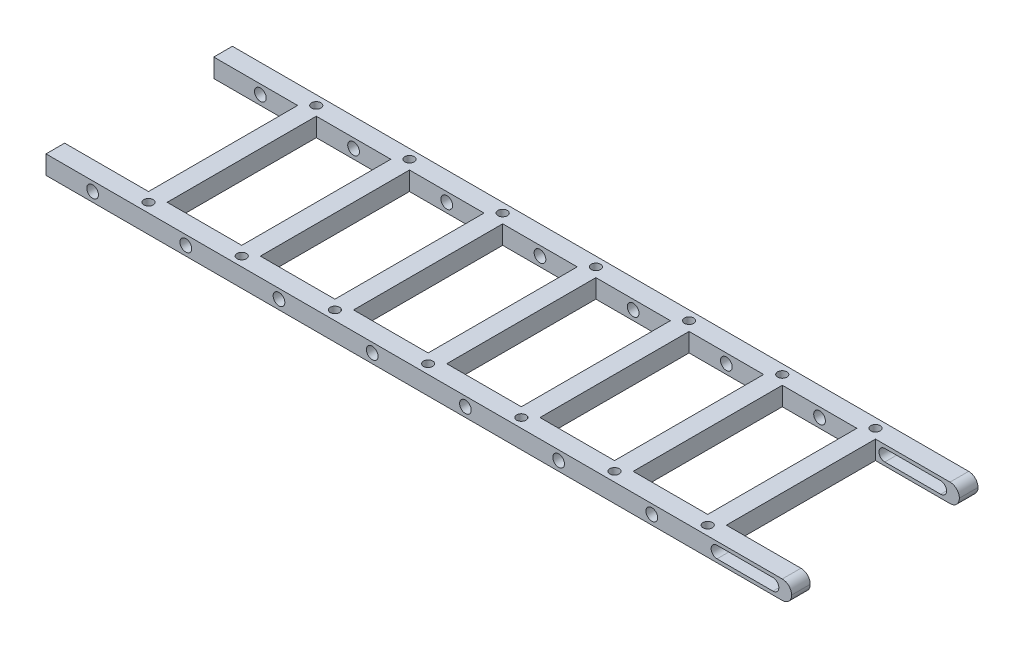
SolidWorks part; units mm, degrees
ref_plane "Front Plane" through (0, 0, 0) normal (0, 0, 1) x (1, 0, 0)
ref_plane "Top Plane" through (0, 0, 0) normal (0, 1, 0) x (1, 0, 0)
ref_plane "Right Plane" through (0, 0, 0) normal (1, 0, 0) x (0, 0, -1)
sketch "Sketch1" plane through (0, 0, 0) normal (0, 1, 0) x (1, 0, 0)
  line L0 (-127, 25.4) -> (-98.425, 25.4)
  line L1 (-127, 31.75) -> (127, 31.75)
  line L2 (-127, 31.75) -> (-127, 25.4)
  line L3 (-127, -31.75) -> (127, -31.75)
  line L4 (127, 31.75) -> (127, 25.4)
  line L8 (-127, -25.4) -> (-98.425, -25.4)
  line L10 (0, 31.75) -> (0, -31.75) construction
  line L11 (-3.175, 25.4) -> (-3.175, -25.4)
  line L12 (98.425, 25.4) -> (98.425, -25.4)
  line L14 (-3.175, 31.75) -> (-3.175, -31.75) construction
  line L15 (-28.575, 25.4) -> (-28.575, -25.4)
  line L16 (-34.925, 25.4) -> (-34.925, -25.4)
  line L17 (-60.325, 25.4) -> (-60.325, -25.4)
  line L18 (-66.675, 25.4) -> (-66.675, -25.4)
  line L19 (-92.075, 25.4) -> (-92.075, -25.4)
  line L22 (-98.425, 25.4) -> (-98.425, -25.4)
  line L23 (-127, -25.4) -> (-127, -31.75)
  line L24 (127, -25.4) -> (127, -31.75)
  line L26 (92.075, 25.4) -> (92.075, -25.4)
  line L27 (66.675, 25.4) -> (66.675, -25.4)
  line L28 (60.325, 25.4) -> (60.325, -25.4)
  line L29 (34.925, 25.4) -> (34.925, -25.4)
  line L30 (28.575, 25.4) -> (28.575, -25.4)
  line L31 (3.175, 25.4) -> (3.175, -25.4)
  line L34 (-92.075, 25.4) -> (-66.675, 25.4)
  line L35 (-92.075, -25.4) -> (-66.675, -25.4)
  line L36 (-28.575, -25.4) -> (-3.175, -25.4)
  line L37 (-60.325, 25.4) -> (-34.925, 25.4)
  line L38 (-28.575, 25.4) -> (-3.175, 25.4)
  line L39 (3.175, 25.4) -> (28.575, 25.4)
  line L40 (3.175, -25.4) -> (28.575, -25.4)
  line L41 (34.925, -25.4) -> (60.325, -25.4)
  line L42 (34.925, 25.4) -> (60.325, 25.4)
  line L43 (66.675, 25.4) -> (92.075, 25.4)
  line L44 (66.675, -25.4) -> (92.075, -25.4)
  line L47 (98.425, -25.4) -> (127, -25.4)
  line L48 (98.425, 25.4) -> (127, 25.4)
  line L49 (-60.325, -25.4) -> (-34.925, -25.4)
  point P0 (0, 0)
  point P16 (0, 0)
  point P18 (0, 0)
  dimension "D1" = 63.5
  dimension "D2" = 127
  dimension "D4" = 3.175
  dimension "D3" = 6.35
  dimension "D14" = 6.35
  dimension "D5" = 6.35
  dimension "D6" = 25.4
  dimension "D7" = 6.35
  dimension "D8" = 25.4
  dimension "D9" = 6.35
  dimension "D10" = 25.4
extrude "Boss-Extrude1" add sketch "Sketch1" against normal blind 6.35
sketch "Sketch2" plane through (0, 0, 31.75) normal (0, 0, 1) x (1, 0, 0)
  line L0 (-111.125, 0) -> (-111.125, -6.35) construction
  line L1 (0, 0) -> (0, -6.35) construction
  line L3 (-127, -6.35) -> (127, -6.35) construction
  line L15 (-66.675, 0) -> (-92.075, 0)
  line L16 (-92.075, 0) -> (-92.075, -6.35)
  line L17 (-92.075, -6.35) -> (-66.675, -6.35)
  line L18 (-66.675, -6.35) -> (-66.675, 0)
  line L19 (-66.675, 0) -> (-92.075, 0) construction
  line L20 (-92.075, 0) -> (-92.075, -6.35) construction
  line L21 (-92.075, -6.35) -> (-66.675, -6.35) construction
  line L22 (-66.675, -6.35) -> (-66.675, 0) construction
  circle A7 centre (-79.375, -3.175) radius 1.9939
  circle A8 centre (-47.625, -3.175) radius 1.9939
  circle A9 centre (-15.875, -3.175) radius 1.9939
  circle A15 centre (-111.125, -3.175) radius 1.9939
  circle A16 centre (15.875, -3.175) radius 1.9939
  circle A17 centre (47.625, -3.175) radius 1.9939
  circle A18 centre (79.375, -3.175) radius 1.9939
  circle A19 centre (111.125, -3.175) radius 1.9939
  point P3 (-79.375, 0)
  point P8 (-92.075, -3.175)
  dimension "D4" = 0
  dimension "D13" = 3.9878
  dimension "D14" = 3.9878
  dimension "D15" = 3.9878
  dimension "D2" = 3.9878
  dimension "D9" = 31.75
  dimension "D10" = 31.75
  dimension "D3" = 31.75
extrude "Cut-Extrude1" cut sketch "Sketch2" against normal up to surface (63.5 mm away) contours A15 | A7 | A8 | A17 | A9 | A16 | A19 | A18 region at (-79.375, -3.175, 31.75) region at (-47.625, -3.175, 31.75) region at (-111.125, -3.175, 31.75) region at (47.625, -3.175, 31.75) up to face at (0, -3.175, -31.75)
sketch "Sketch3" plane through (0, 0, 31.75) normal (0, 0, 1) x (1, 0, 0)
  line L0 (101.6, -3.175) -> (120.65, -3.175) construction
  line L1 (101.6, -1.175) -> (120.65, -1.175)
  line L2 (101.6, -5.175) -> (120.65, -5.175)
  arc A0 (101.6, -1.175) -> (101.6, -5.175) centre (101.6, -3.175) ccw
  arc A1 (120.65, -5.175) -> (120.65, -1.175) centre (120.65, -3.175) ccw
  circle A2 centre (111.125, -3.175) radius 1.9939 construction
  circle A3 centre (111.125, -3.175) radius 1.9939 construction
  point P3 (111.125, -3.175)
  dimension "D2" = 2
  dimension "D1" = 19.05
extrude "Cut-Extrude2" cut sketch "Sketch3" against normal through all
sketch "Sketch4" plane through (0, 0, 0) normal (0, 1, 0) x (1, 0, 0)
  line L0 (-92.075, 0) -> (-98.425, 0) construction
  line L1 (-92.075, 25.4) -> (-92.075, -25.4) construction
  line L2 (-127, 28.575) -> (127, 28.575) construction
  line L3 (-127, -28.575) -> (127, -28.575) construction
  line L4 (-127, 31.75) -> (-127, 25.4) construction
  line L5 (-127, -25.4) -> (-127, -31.75) construction
  line L6 (127, 25.4) -> (127, 31.75) construction
  line L12 (-98.425, -25.4) -> (-127, -25.4)
  line L13 (127, -31.75) -> (127, -25.4)
  line L14 (-127, -31.75) -> (127, -31.75)
  line L15 (127, -31.75) -> (127, -25.4)
  line L16 (127, -25.4) -> (98.425, -25.4)
  line L17 (98.425, -25.4) -> (98.425, 25.4)
  line L18 (98.425, 25.4) -> (127, 25.4)
  line L19 (127, 25.4) -> (127, 31.75)
  line L20 (127, 31.75) -> (-127, 31.75)
  line L21 (127, 25.4) -> (127, 31.75)
  line L22 (-127, 25.4) -> (-98.425, 25.4)
  line L23 (-98.425, 25.4) -> (-98.425, -25.4)
  line L24 (-98.425, -25.4) -> (-127, -25.4) construction
  line L26 (-127, -31.75) -> (127, -31.75) construction
  line L28 (127, -25.4) -> (98.425, -25.4) construction
  line L29 (98.425, -25.4) -> (98.425, 25.4) construction
  line L30 (98.425, 25.4) -> (127, 25.4) construction
  line L32 (127, 31.75) -> (-127, 31.75) construction
  line L34 (-127, 25.4) -> (-98.425, 25.4) construction
  line L35 (-98.425, 25.4) -> (-98.425, -25.4) construction
  line L40 (-127, 31.75) -> (-127, 25.4)
  line L41 (-127, 31.75) -> (-127, 25.4)
  line L42 (-127, -25.4) -> (-127, -31.75)
  line L43 (-127, -25.4) -> (-127, -31.75)
  circle A0 centre (-95.25, 28.575) radius 1.5875
  circle A2 centre (-63.5, 28.575) radius 1.5875
  circle A3 centre (-31.75, 28.575) radius 1.5875
  circle A4 centre (0, 28.575) radius 1.5875
  circle A5 centre (31.75, 28.575) radius 1.5875
  circle A6 centre (63.5, 28.575) radius 1.5875
  circle A7 centre (95.25, 28.575) radius 1.5875
  circle A8 centre (95.25, -28.575) radius 1.5875
  circle A9 centre (63.5, -28.575) radius 1.5875
  circle A10 centre (31.75, -28.575) radius 1.5875
  circle A11 centre (0, -28.575) radius 1.5875
  circle A12 centre (-31.75, -28.575) radius 1.5875
  circle A13 centre (-63.5, -28.575) radius 1.5875
  circle A14 centre (-95.25, -28.575) radius 1.5875
  point P10 (-95.25, 28.575)
  point P14 (-95.25, 0)
  point P16 (0, 0)
  point P26 (0, 0)
  point P52 (-95.25, -28.575)
  point P53 (0, 0)
  point P54 (0, 0)
  point P55 (0, 0)
  point P56 (-127, 28.575)
  point P59 (-127, -28.575)
  point P62 (127, -28.575)
  point P63 (127, 28.575)
  dimension "D2" = 3.175
  dimension "D5" = 31.75
  dimension "D1" = 0
  dimension "D4" = 7
extrude "Cut-Extrude3" cut sketch "Sketch4" against normal through all contours A14 | A0 | A2 | A3 | A13 | A12 | A4 | A11 | A5 | A6 | A7 | A8 | A9 | A10
fillet "Fillet1" radius 3.175 4 edges at (127, -6.35, -28.575) (127, 0, -28.575) (127, -6.35, 28.575) (127, 0, 28.575)
sketch "Sketch6" plane through (-127, 0, 0) normal (-1, 0, 0) x (0, 0, 1)
  line L0 (-31.75, 0) -> (-25.4, -6.35) construction
  line L1 (-25.4, 0) -> (-31.75, -6.35) construction
  line L2 (31.75, 0) -> (25.4, -6.35) construction
  line L3 (25.4, 0) -> (31.75, -6.35) construction
  circle A0 centre (-28.575, -3.175) radius 1.5875
  circle A1 centre (28.575, -3.175) radius 1.5875
  dimension "D1" = 3.175
  dimension "D2" = 3.175
extrude "Cut-Extrude4" cut sketch "Sketch6" against normal blind 6.35
